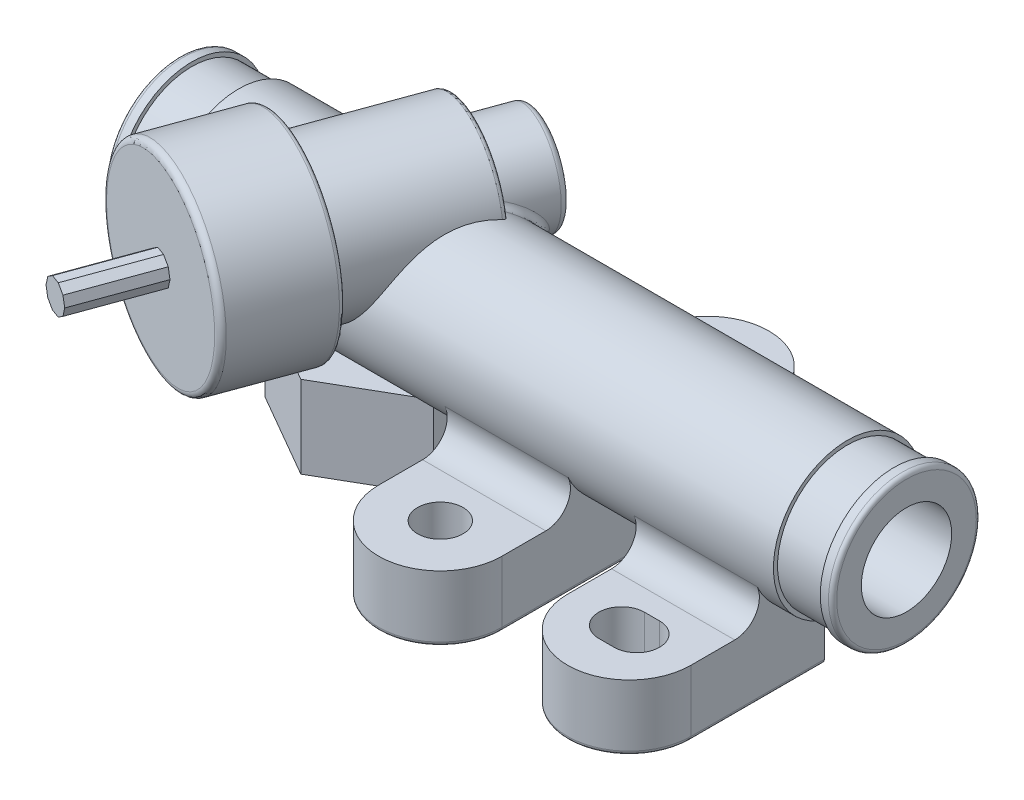
SolidWorks part; units mm, degrees
material "6061-T6 (SS)"
ref_plane "Front Plane" through (0, 0, 0) normal (0, 0, 1) x (1, 0, 0)
ref_plane "Top Plane" through (0, 0, 0) normal (0, 1, 0) x (1, 0, 0)
ref_plane "Right Plane" through (0, 0, 0) normal (1, 0, 0) x (0, 0, -1)
sketch "Sketch1" plane through (0, 0, 0) normal (1, 0, 0) x (0, 0, -1)
  circle A0 centre (0, 0) radius 11
  circle A1 centre (0, 0) radius 18
  dimension "D1" = 22
  dimension "D2" = 36
extrude "Boss-Extrude1" add sketch "Sketch1" along normal blind 177
ref_plane "Plane1" through (0, -18, 0) normal (0, 1, 0) x (1, 0, 0)
sketch "Sketch2" plane through (0, -18, 0) normal (0, 1, 0) x (1, 0, 0)
  line L0 (96, 32.5) -> (96, -32.5)
  line L2 (0, 0) -> (124.4097, 0)
  line L3 (127, -32.5) -> (127, 0)
  line L6 (96, 32.5) -> (96, -32.5) construction
  line L7 (111, 32.5) -> (111, -32.5)
  line L8 (81, 32.5) -> (81, -32.5)
  line L14 (140.15, -32.5) -> (143.85, -32.5) construction
  line L15 (140.15, -38.05) -> (143.85, -38.05)
  line L16 (140.15, -26.95) -> (143.85, -26.95)
  line L17 (127, 0) -> (157, 0)
  line L18 (157, 0) -> (157, -32.5)
  line L19 (96, -32.5) -> (142, -32.5) construction
  circle A0 centre (96, 32.5) radius 5
  circle A1 centre (96, -32.5) radius 5.55
  arc A5 (111, 32.5) -> (81, 32.5) centre (96, 32.5) ccw
  arc A6 (81, -32.5) -> (111, -32.5) centre (96, -32.5) ccw
  arc A9 (140.15, -38.05) -> (140.15, -26.95) centre (140.15, -32.5) cw
  arc A10 (143.85, -26.95) -> (143.85, -38.05) centre (143.85, -32.5) cw
  arc A14 (127, -32.5) -> (157, -32.5) centre (142, -32.5) ccw
  point P5 (134.6, -32.5)
  point P9 (96, 0)
  point P33 (142, -32.5)
  dimension "D1" = 65
  dimension "D2" = 10
  dimension "D3" = 11.1
  dimension "D6" = 7.4
  dimension "D8" = 46
  dimension "D7" = 15
  dimension "D4" = 35
  dimension "D5" = 32.5
extrude "Boss-Extrude2" add sketch "Sketch2" against normal blind 14 and the other way blind 2 contours A10 L16 A9 L15 | A14 L18 L17 L3 | L8 A6 L7 A5 | A0 | A1 region at (142, -18, 32.5)
sketch "Sketch3" plane through (177, 0, 0) normal (1, 0, 0) x (0, 0, -1)
  circle A0 centre (0, 0) radius 11
extrude "Cut-Extrude1" [suppressed] cut sketch "Sketch3" against normal through all
ref_plane "Plane2" through (50, 0, 0) normal (-1, 0, 0) x (0, 0, 1)
sketch "Sketch4" plane through (50, 0, 0) normal (-1, 0, 0) x (0, 0, 1)
  line L0 (0, 0) -> (0, 8.423)
ref_plane "Plane3" through (5.8489, 0, -16.0697) normal (-0.342, 0, 0.9397) x (0, 1, 0)
sketch "Sketch5" plane through (5.8489, 0, -16.0697) normal (-0.342, 0, 0.9397) x (0, 1, 0)
  line L0 (13.0934, -50) -> (0, -50) construction
  line L1 (0, -166.3256) -> (0, 0) construction
  circle A0 centre (13.0934, -50) radius 17.5
  dimension "D1" = 35
  dimension "D2" = 50
extrude "Boss-Extrude3" add sketch "Sketch5" along normal blind 20 and the other way blind 14
sketch "Sketch6" plane through (-0.9915, 0, 2.7242) normal (-0.342, 0, 0.9397) x (0.9397, 0, 0.342)
  circle A0 centre (50, 13.0934) radius 23.5
  dimension "D1" = 47
extrude "Boss-Extrude4" add sketch "Sketch6" along normal blind 24
sketch "Sketch7" plane through (10.6372, 0, -29.2254) normal (0.342, 0, -0.9397) x (-0.9397, 0, -0.342)
  circle A0 centre (-50, 13.0934) radius 12
  dimension "D1" = 24
extrude "Boss-Extrude5" add sketch "Sketch7" along normal blind 14
fillet "Fillet2" [suppressed] radius 10
sketch "Sketch8" plane through (-9.2, 0, 25.2768) normal (-0.342, 0, 0.9397) x (0.9397, 0, 0.342)
  line L1 (53.8116, 13.0934) -> (53.0836, 15.3337)
  line L2 (53.0836, 15.3337) -> (51.1778, 16.7184)
  line L3 (51.1778, 16.7184) -> (48.8222, 16.7184)
  line L4 (48.8222, 16.7184) -> (46.9164, 15.3337)
  line L5 (46.9164, 15.3337) -> (46.1884, 13.0934)
  line L6 (46.1884, 13.0934) -> (46.9164, 10.853)
  line L7 (46.9164, 10.853) -> (48.8222, 9.4684)
  line L8 (48.8222, 9.4684) -> (51.1778, 9.4684)
  line L9 (51.1778, 9.4684) -> (53.0836, 10.853)
  line L10 (53.0836, 10.853) -> (53.8116, 13.0934)
  circle A0 centre (50, 13.0934) radius 3.625 construction
extrude "Boss-Extrude6" add sketch "Sketch8" along normal blind 20
sketch "Sketch9" plane through (0, 0, 0) normal (0, 1, 0) x (1, 0, 0)
  line L0 (0, -18) -> (25.8906, -18) construction
  line L1 (3, -18) -> (14.4, -18)
  line L2 (3, -18) -> (3, -17)
  line L3 (3, -17) -> (14.4, -17)
  line L4 (14.4, -18) -> (14.4, -17)
  line L5 (177, -18) -> (177, 18) construction
  line L6 (174, -18) -> (162.6, -18)
  line L7 (174, -18) -> (174, -17)
  line L8 (174, -17) -> (162.6, -17)
  line L9 (162.6, -18) -> (162.6, -17)
  line L10 (0, 18) -> (0, -18) construction
  dimension "D1" = 1
  dimension "D2" = 14.4
  dimension "D3" = 1
  dimension "D4" = 14.4
  dimension "D5" = 3
  dimension "D6" = 3
revolve "Cut-Revolve1" cut sketch "Sketch9" angle 360 about axis through (177, 0, 0) along (-1, 0, 0)
fillet "Fillet3" radius 1.5 5 edges at (66.893, 3.2067, -17.7121) (54.0295, 24.4682, -13.4319) (51.1338, 13.0934, -29.3843) (59.8674, 13.0934, 50.4153) (59.0824, 23.6869, 24.5893)
fillet "Fillet4" radius 1 11 edges at (111, -32, 0) (81, -32, 0) (127, -32, 16.25) (157, -32, 16.25) (51.8457, 29.4783, -14.2267) (64.9344, 25.1743, 26.7192) (0, 0, -18) (96, -32, -47.5) (177, 0, -18) (142, -32, 47.5) (96, -32, 47.5)
fillet "Fillet5" radius 6 3 edges at (142, -16, 8.2462) (96, -16, -8.2462) (96, -16, 8.2462)
sketch "Sketch10" plane through (0, 0, 0) normal (-1, 0, 0) x (0, 0, 1)
  circle A0 centre (0, 0) radius 11
  circle A2 centre (0, 0) radius 11 construction
extrude "Cut-Extrude2" cut sketch "Sketch10" against normal blind 100
sketch3d "3DSketch1"
  line L0 (177, 0, 0) -> (0, 0, 0) construction
  line L1 (177, 0, 0) -> (0, 0, 0) construction
  line L2 (40.0486, 13.0934, 36.1576) -> (25.9934, 13.0934, 74.7738) construction
  line L3 (38.2977, 13.0934, 40.9683) -> (45.6511, 13.0934, 20.7649) construction
  point P0 (88.5, 0, 0)
  point P7 (88.5, 0, 0)
sketch "Sketch11" plane through (0, 0, 0) normal (1, 0, 0) x (0, 0, -1)
  line L0 (47.2071, -31.7071) -> (-26.6695, -93.6969)
  line L1 (32.5, -32) -> (-32.5, -32) construction
  line L2 (0, 0) -> (35.1175, -41.8515) construction
  arc A0 (46.5, -32) -> (47.5, -31) centre (46.5, -31) ccw construction
  dimension "D1" = 40
  dimension "D2" = 54.6332
sketch "Sketch12" plane through (0, -32, 0) normal (0, -1, 0) x (1, 0, 0)
  line L0 (177, 0) -> (0, 0) construction
  line L1 (53.2089, 23.6714) -> (32.7089, 11.8357)
  line L2 (32.7089, 11.8357) -> (32.7089, -11.8357)
  line L3 (32.7089, -11.8357) -> (53.2089, -23.6714)
  line L4 (53.2089, -23.6714) -> (73.7089, -11.8357)
  line L5 (73.7089, -11.8357) -> (73.7089, 11.8357)
  line L6 (73.7089, 11.8357) -> (53.2089, 23.6714)
  line L7 (57.2798, -11.1847) -> (46.5061, 18.4156) construction
  circle A0 centre (53.2089, 0) radius 20.5 construction
  dimension "D1" = 41
extrude "Boss-Extrude7" add sketch "Sketch12" against normal blind 20
